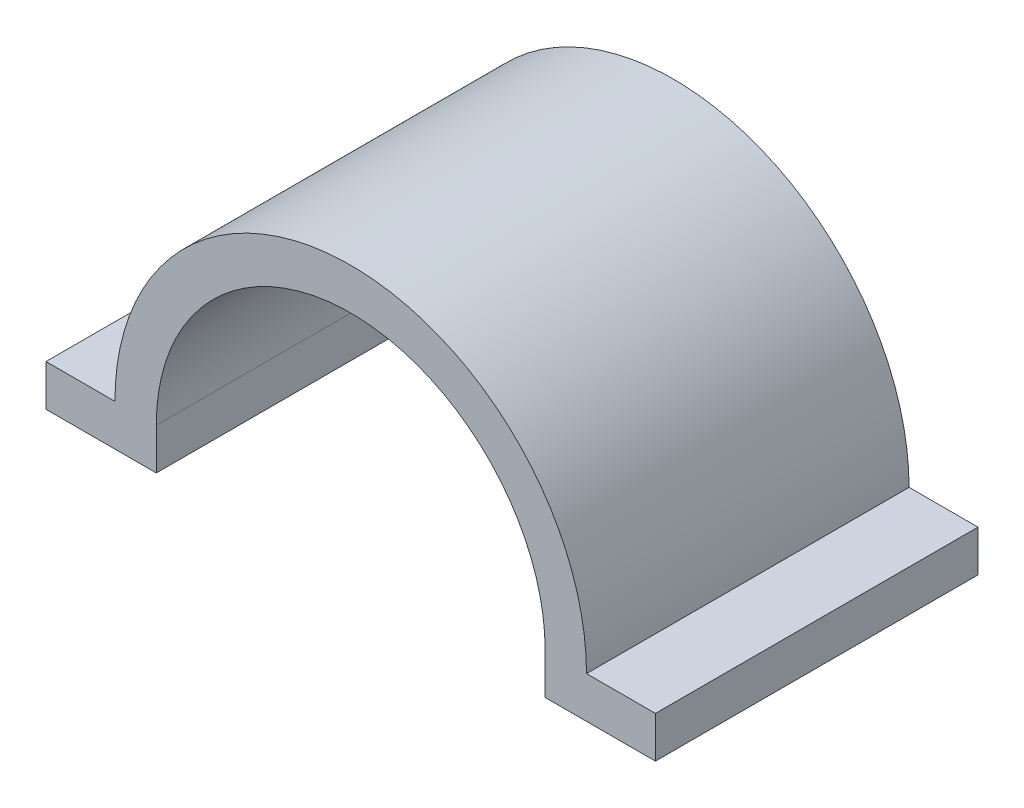
SolidWorks part; units mm, degrees
ref_plane "Front Plane" through (0, 0, 0) normal (0, 0, 1) x (1, 0, 0)
ref_plane "Top Plane" through (0, 0, 0) normal (0, 1, 0) x (1, 0, 0)
ref_plane "Right Plane" through (0, 0, 0) normal (1, 0, 0) x (0, 0, -1)
sketch "Sketch1" plane through (0, 0, 0) normal (0, 0, 1) x (1, 0, 0)
  line L2 (-17.1031, 0) -> (-22.1031, 0)
  line L3 (-22.1031, 0) -> (-22.1031, -3)
  line L4 (-22.1031, -3) -> (-14.1031, -3)
  line L5 (-14.1031, -3) -> (-14.1031, 0)
  line L6 (14.1031, 0) -> (14.1031, -3)
  line L7 (14.1031, -3) -> (22.1031, -3)
  line L8 (22.1031, -3) -> (22.1031, 0)
  line L9 (22.1031, 0) -> (17.1031, 0)
  arc A0 (14.1031, 0) -> (-14.1031, 0) centre (0, 0) ccw
  arc A1 (17.1031, 0) -> (-17.1031, 0) centre (0, 0) ccw
  dimension "D1" = 3
  dimension "D2" = 3
  dimension "D3" = 3
extrude "Boss-Extrude1" add sketch "Sketch1" along normal blind 23.4
